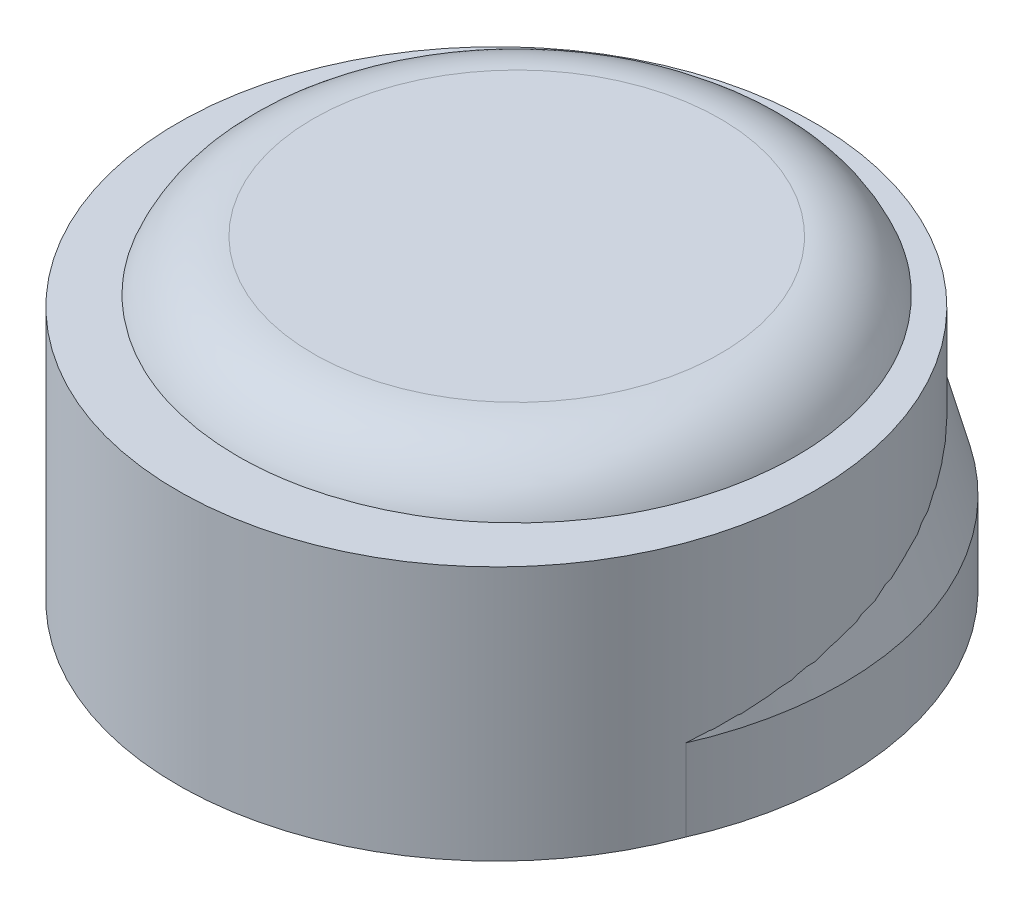
SolidWorks part; units mm, degrees
ref_plane "Front" through (0, 0, 0) normal (0, 0, 1) x (1, 0, 0)
ref_plane "Top" through (0, 0, 0) normal (0, 1, 0) x (1, 0, 0)
ref_plane "Right" through (0, 0, 0) normal (1, 0, 0) x (0, 0, -1)
ref_axis "side-side" through (80.9, 0, 0) along (-1, 0, 0)
ref_axis "up-down" through (0, 50, 0) along (0, -1, 0)
ref_axis "front-back" through (0, 0, -80.9) along (0, 0, 1)
sketch "Sketch1" plane through (0, 0, 0) normal (0, 0, 1) x (1, 0, 0)
  line L0 (0, 0) -> (0, -22.0589) construction
  line L1 (-1.4732, 0) -> (-8.128, 0)
  line L2 (-1.4732, 0) -> (-1.4732, 7.62)
  line L3 (-1.4732, 7.62) -> (-5.0715, 7.62)
  line L4 (-8.128, 0) -> (-8.128, 2.032)
  line L5 (-8.128, 2.032) -> (-7.0343, 6.1139)
  line L6 (-5.1617, 2.032) -> (-6.0243, 2.032) construction
  line L7 (-6.0243, 2.032) -> (-5.0715, 5.588) construction
  line L8 (-5.0715, 5.588) -> (-5.588, 5.588) construction
  line L9 (-5.588, 5.588) -> (-5.588, 2.54) construction
  line L10 (-5.588, 2.54) -> (-3.5052, 2.54) construction
  line L11 (-3.5052, 2.54) -> (-3.5052, 2.032) construction
  line L12 (-1.4732, 2.032) -> (-8.128, 2.032) construction
  line L13 (-5.588, 2.54) -> (-5.1617, 2.032) construction
  arc A0 (-7.0343, 6.1139) -> (-5.0715, 7.62) centre (-5.0715, 5.588) cw
  point P9 (-5.5479, 3.81)
  dimension "D1" = 2.032
  dimension "D2" = 15
  dimension "D3" = 16.256
  dimension "D4" = 7.62
  dimension "D5" = 2.032
  dimension "D6" = 2.9464
  dimension "D8" = 5.588
  dimension "D9" = 5.08
  dimension "D10" = 2.032
  dimension "D11" = 2.032
  dimension "D12" = 2.032
  dimension "D13" = 50
  dimension "D7" = 2.032
revolve "Revolve1" add sketch "Sketch1" angle 360 about L0
sketch "Sketch2" plane through (0, 7.62, 0) normal (0, 1, 0) x (1, 0, 0)
  line L1 (-4.8393, 0) -> (-2.4197, -4.191)
  line L2 (-2.4197, -4.191) -> (2.4197, -4.191)
  line L3 (2.4197, -4.191) -> (4.8393, 0)
  line L4 (4.8393, 0) -> (2.4197, 4.191)
  line L5 (2.4197, 4.191) -> (-2.4197, 4.191)
  line L6 (-2.4197, 4.191) -> (-4.8393, 0)
  circle A0 centre (0, 0) radius 4.191 construction
  dimension "D1" = 8.382
extrude "Cut-Extrude1" [suppressed] cut sketch "Sketch2" against normal blind 3.81
other "DeleteFace1" face at (-1.4732, 7.62, 0) and patch yes
sketch "Sketch3" plane through (0, 0, 0) normal (0, -1, 0) x (1, 0, 0)
  circle A2 centre (0, 2) radius 3.873
  circle A3 centre (0, 2) radius 3.873
  dimension "D1" = 0.127
extrude "Boss-Extrude1" add sketch "Sketch3" along normal blind 1.778
sketch "Sketch4" plane through (0, 0, 0) normal (0, -1, 0) x (1, 0, 0)
  circle A0 centre (0, 0.508) radius 7.9375
  dimension "D1" = 15.875
  dimension "D2" = 0.508
extrude "Boss-Extrude2" add sketch "Sketch4" against normal blind 6.35 separate body
sketch "Sketch5" plane through (0, 0, 0) normal (0, 1, 0) x (1, 0, 0)
  circle A1 centre (0, -0.508) radius 7.9375 construction
  circle A2 centre (0, -0.508) radius 7.9375
  circle A3 centre (0, -2) radius 3.873 construction
  circle A4 centre (0, -2) radius 3.873
  dimension "D1" = 1.492
